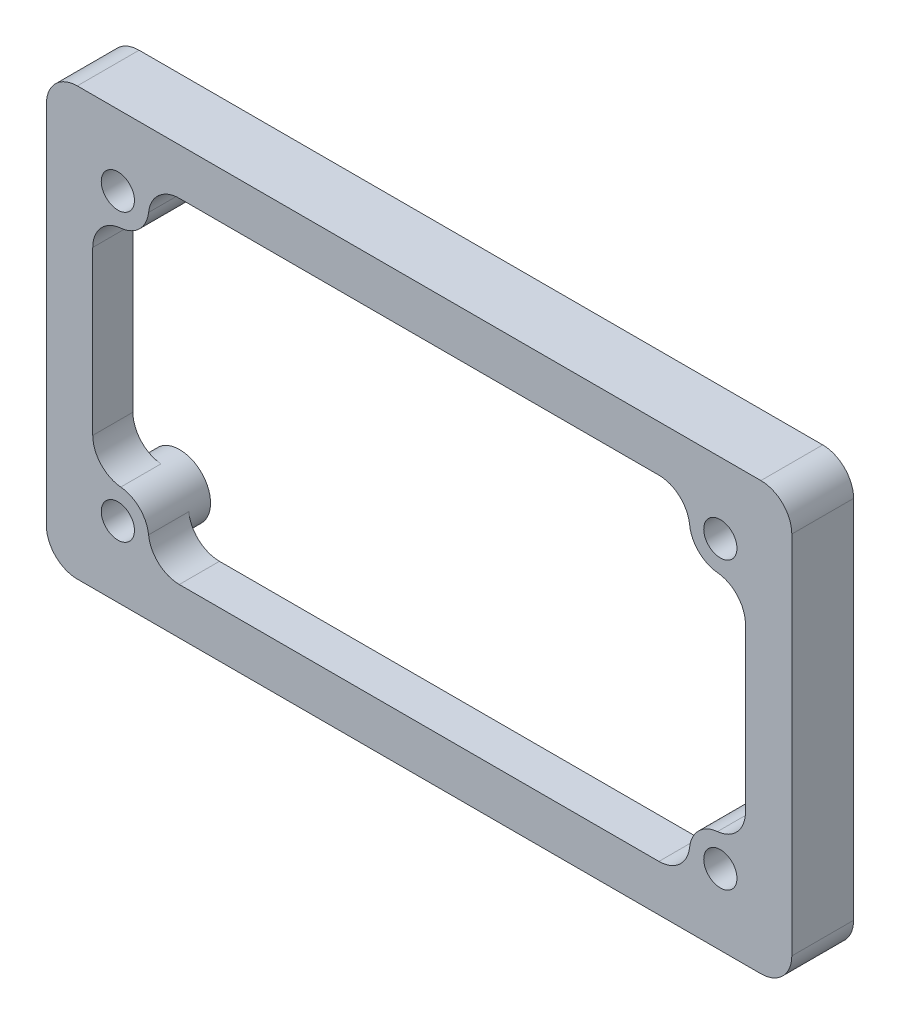
SolidWorks part; units mm, degrees
material "ABS"
ref_plane "Front Plane" through (0, 0, 0) normal (0, 0, 1) x (1, 0, 0)
ref_plane "Top Plane" through (0, 0, 0) normal (0, 1, 0) x (1, 0, 0)
ref_plane "Right Plane" through (0, 0, 0) normal (1, 0, 0) x (0, 0, -1)
sketch "Sketch1" plane through (0, 0, 0) normal (0, 0, 1) x (1, 0, 0)
  line L0 (-1.5, 26.15) -> (46.75, 26.15)
  line L1 (0, 0) -> (45.25, 0)
  line L2 (0, 0) -> (0, 24.65)
  line L3 (0, 24.65) -> (45.25, 24.65)
  line L4 (45.25, 0) -> (45.25, 24.65)
  line L5 (46.75, -1.5) -> (46.75, 26.15)
  line L6 (-1.5, -1.5) -> (46.75, -1.5)
  line L7 (-1.5, -1.5) -> (-1.5, 26.15)
  dimension "D1" = 24.65
  dimension "D2" = 45.25
  dimension "D3" = 1.5
extrude "Main Body" add sketch "Sketch1" along normal blind 4
sketch "Sketch3" plane through (0, 0, 4) normal (0, 0, 1) x (1, 0, 0)
  line L0 (0, 24.65) -> (0, 0)
  line L1 (0, 0) -> (45.25, 0)
  line L2 (45.25, 0) -> (45.25, 24.65)
  line L3 (45.25, 24.65) -> (0, 24.65)
  line L4 (1.5, 23.15) -> (1.5, 1.5)
  line L5 (1.5, 1.5) -> (43.75, 1.5)
  line L6 (43.75, 1.5) -> (43.75, 23.15)
  line L7 (43.75, 23.15) -> (1.5, 23.15)
  dimension "D1" = 1.5
extrude "Boss-Extrude2" add sketch "Sketch3" against normal offset from surface (2.6 mm away) 1.4 up to face at (22.625, 12.325, 0)
sketch "Sketch4" plane through (0, 0, 1.4) normal (0, 0, -1) x (-1, 0, 0)
  line L0 (0, 12.325) -> (-45.25, 12.325) construction
  line L1 (0, 24.65) -> (0, 0) construction
  line L2 (-45.25, 0) -> (-45.25, 24.65) construction
  line L3 (-22.625, 12.325) -> (-22.625, 24.65) construction
  line L4 (-45.25, 24.65) -> (0, 24.65) construction
  line L5 (-1.125, 21.575) -> (-1.125, 23.575)
  line L6 (-1.125, 23.575) -> (-3.125, 23.575)
  line L7 (-1.125, 1.075) -> (-3.125, 1.075)
  line L8 (-1.125, 3.075) -> (-1.125, 1.075)
  line L9 (-44.125, 3.075) -> (-44.125, 1.075)
  line L10 (-44.125, 1.075) -> (-42.125, 1.075)
  line L11 (-44.125, 23.575) -> (-42.125, 23.575)
  line L12 (-44.125, 21.575) -> (-44.125, 23.575)
  arc A0 (-3.125, 23.575) -> (-1.125, 21.575) centre (-3.125, 21.575) ccw
  arc A1 (-3.125, 1.075) -> (-1.125, 3.075) centre (-3.125, 3.075) cw
  arc A2 (-42.125, 1.075) -> (-44.125, 3.075) centre (-42.125, 3.075) ccw
  arc A3 (-42.125, 23.575) -> (-44.125, 21.575) centre (-42.125, 21.575) cw
  dimension "D1" = 4
  dimension "D2" = 39
  dimension "D3" = 18.5
extrude "Boss-Extrude3" add sketch "Sketch4" along normal up to surface (1.4 mm away) and the other way up to surface (2.6 mm away) up to face at (22.625, 12.325, 0) other way up to face at (22.625, 12.325, 4)
sketch "Sketch5" plane through (0, 0, 0) normal (0, 0, -1) x (-1, 0, 0)
  line L0 (-1.125, 23.575) -> (-1.125, 21.575) construction
  line L1 (-1.125, 23.575) -> (-3.125, 23.575) construction
  line L2 (-1.125, 23.575) -> (-1.125, 21.575)
  line L3 (-1.125, 23.575) -> (-3.125, 23.575)
  line L4 (-1.125, 1.075) -> (-1.125, 3.075) construction
  line L5 (-3.125, 1.075) -> (-1.125, 1.075) construction
  line L6 (-44.125, 1.075) -> (-42.125, 1.075) construction
  line L7 (-44.125, 3.075) -> (-44.125, 1.075) construction
  line L8 (-42.125, 23.575) -> (-44.125, 23.575) construction
  line L9 (-44.125, 23.575) -> (-44.125, 21.575) construction
  line L10 (-1.125, 1.075) -> (-1.125, 3.075)
  line L11 (-3.125, 1.075) -> (-1.125, 1.075)
  line L12 (-44.125, 1.075) -> (-42.125, 1.075)
  line L13 (-44.125, 3.075) -> (-44.125, 1.075)
  line L14 (-42.125, 23.575) -> (-44.125, 23.575)
  line L15 (-44.125, 23.575) -> (-44.125, 21.575)
  circle A0 centre (-3.125, 21.575) radius 1.075
  circle A1 centre (-3.125, 3.075) radius 1.075
  circle A2 centre (-42.125, 21.575) radius 1.075
  circle A3 centre (-42.125, 3.075) radius 1.075
  arc A4 (-42.125, 23.575) -> (-44.125, 21.575) centre (-42.125, 21.575) ccw
  arc A5 (-44.125, 3.075) -> (-42.125, 1.075) centre (-42.125, 3.075) ccw
  arc A6 (-1.125, 21.575) -> (-3.125, 23.575) centre (-3.125, 21.575) ccw
  arc A7 (-1.125, 3.075) -> (-3.125, 1.075) centre (-3.125, 3.075) cw
  arc A8 (-1.125, 3.075) -> (-3.125, 1.075) centre (-3.125, 3.075) ccw construction
  line M1 (-1.125, 23.575) -> (-3.125, 23.575)
  line M3 (-1.125, 21.575) -> (-1.125, 23.575)
  dimension "D1" = 2.15
extrude "Cut-Extrude1" cut sketch "Sketch5" against normal up to surface (1.4 mm away) contours A6 M3 M1 | A0 | A1 | L10 A7 L11 | A3 | A5 L13 L12 | A2 | A4 L14 L15 region at (1.5717, 23.1283, 0) region at (1.5717, 1.5217, 0) region at (43.6783, 1.5217, 0) region at (43.6783, 23.1283, 0) region at (3.125, 21.575, 0) region at (3.125, 3.075, 0) region at (42.125, 21.575, 0) region at (42.125, 3.075, 0) up to face at (22.625, 12.325, 1.4)
sketch "Sketch6" plane through (0, 0, 1.4) normal (0, 0, -1) x (-1, 0, 0)
  circle A0 centre (-3.125, 21.575) radius 1.075 construction
  circle A1 centre (-3.125, 3.075) radius 1.075 construction
  circle A2 centre (-42.125, 3.075) radius 1.075 construction
  circle A3 centre (-42.125, 21.575) radius 1.075 construction
  circle A4 centre (-3.125, 21.575) radius 1.075
  circle A5 centre (-3.125, 3.075) radius 1.075
  circle A6 centre (-42.125, 3.075) radius 1.075
  circle A7 centre (-42.125, 21.575) radius 1.075
extrude "Cut-Extrude2" cut sketch "Sketch6" against normal through all
fillet "Fillet1" radius 2 16 edges at (43.75, 4.2409, 2.7) (40.8924, 1.5, 2.7) (40.8924, 23.15, 2.7) (43.75, 20.4091, 2.7) (4.3576, 1.5, 2.7) (1.5, 4.2409, 2.7) (1.5, 20.4091, 2.7) (4.3576, 23.15, 2.7) (45.25, 0, 0.7) (46.75, -1.5, 2) (45.25, 24.65, 0.7) (46.75, 26.15, 2) (0, 0, 0.7) (-1.5, -1.5, 2) (-1.5, 26.15, 2) (0, 24.65, 0.7)
ref_point "Point1"
